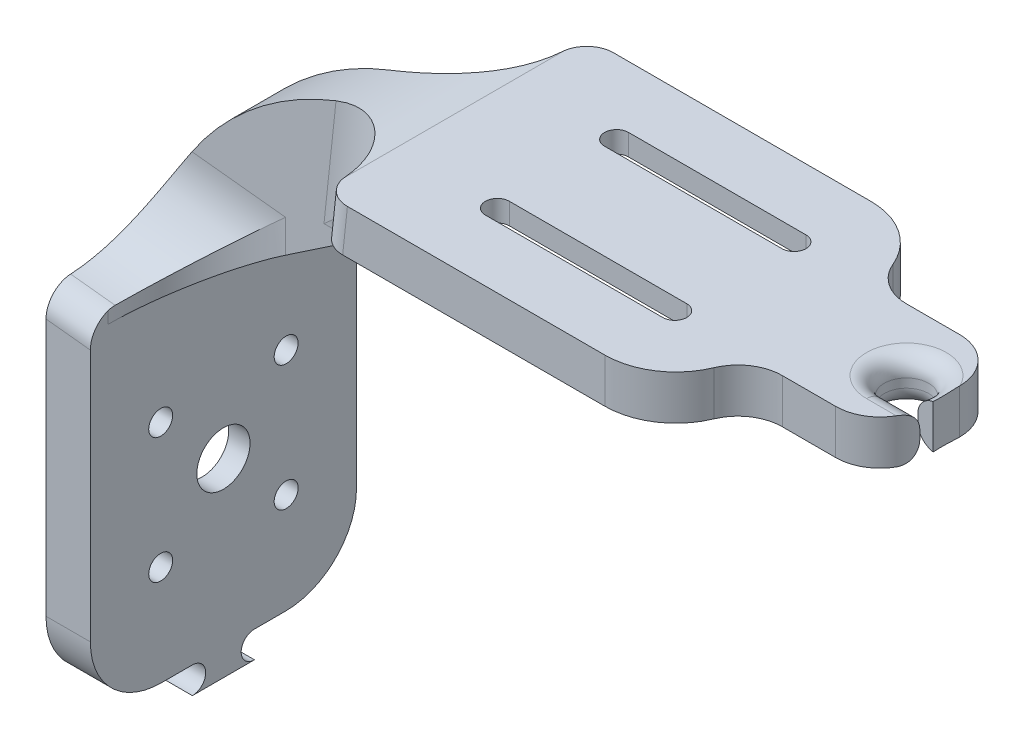
SolidWorks part; units mm, degrees
material "ABS"
ref_plane "Alzado" through (0, 0, 0) normal (0, 0, 1) x (1, 0, 0)
ref_plane "Planta" through (0, 0, 0) normal (0, 1, 0) x (1, 0, 0)
ref_plane "Vista lateral" through (0, 0, 0) normal (1, 0, 0) x (0, 0, -1)
sketch "Croquis1" plane through (0, 0, 0) normal (0, 0, 1) x (1, 0, 0)
  line L0 (0, 0) -> (0, 5)
  line L1 (0, 5) -> (-40, 5)
  line L2 (-40, 5) -> (-71, -20) construction
  line L3 (-71, -20) -> (-71, -60)
  line L4 (-71, -60) -> (-66, -60)
  line L5 (-66, -60) -> (-66, -20.5357)
  line L6 (-66, -20.5357) -> (-40.5357, 0) construction
  line L7 (-40.5357, 0) -> (0, 0)
  line L8 (-53.2679, -10.2679) -> (-37.574, -29.7282) construction
  arc A0 (-40, 5) -> (-71, -20) centre (-37.574, -29.7282) ccw
  arc A1 (-40.5357, 0) -> (-66, -20.5357) centre (-37.574, -29.7282) ccw
  dimension "D1" = 5
  dimension "D2" = 31
  dimension "D4" = 5
  dimension "D5" = 40
  dimension "D6" = 40
  dimension "D7" = 25
  dimension "D8" = 25
extrude "Saliente-Extruir1" add sketch "Croquis1" along normal blind 30
sketch "Croquis2" plane through (0, 5, 0) normal (0, 1, 0) x (1, 0, 0)
  line L0 (0, -30) -> (0, 0) construction
  line L1 (-18.4, -15) -> (-18.4, -12) construction
  line L2 (-18.4, -12) -> (-11.4, -12) construction
  line L4 (-11.4, -18) -> (-25.4, -18) construction
  line L6 (-25.4, -12) -> (-18.4, -12) construction
  line L7 (-18.4, -15) -> (-18.4, -8.28) construction
  line L8 (-18.4, -8.28) -> (-18.4, -6.93) construction
  line L9 (-18.4, -6.93) -> (-8.4, -6.93)
  line L11 (-8.4, -9.63) -> (-28.4, -9.63)
  line L13 (-28.4, -6.93) -> (-18.4, -6.93)
  line L14 (-18.4, -15) -> (-21.0577, -15) construction
  line L22 (0, -15) -> (-18.4, -15) construction
  line L23 (-8.4, -20.37) -> (-28.4, -20.37)
  line L24 (-18.4, -23.07) -> (-8.4, -23.07)
  line L25 (-28.4, -23.07) -> (-18.4, -23.07)
  circle A0 centre (-18.4, -15) radius 18.4 construction
  arc A1 (-25.4, -18) -> (-25.4, -12) centre (-25.4, -15) cw construction
  arc A2 (-11.4, -18) -> (-11.4, -12) centre (-11.4, -15) ccw construction
  arc A3 (-8.4, -9.63) -> (-8.4, -6.93) centre (-8.4, -8.28) ccw
  arc A4 (-28.4, -9.63) -> (-28.4, -6.93) centre (-28.4, -8.28) cw
  arc A9 (-8.4, -20.37) -> (-8.4, -23.07) centre (-8.4, -21.72) cw
  arc A10 (-28.4, -20.37) -> (-28.4, -23.07) centre (-28.4, -21.72) ccw
  dimension "D1" = 36.8
  dimension "D5" = 3
  dimension "D6" = 3
  dimension "D11" = 1.35
  dimension "D12" = 1.35
  dimension "D2" = 18.4
  dimension "D3" = 3
  dimension "D4" = 6
  dimension "D7" = 7
  dimension "D8" = 7
  dimension "D9" = 6.72
  dimension "D10" = 2.7
  dimension "D13" = 10
  dimension "D14" = 10
extrude "Cortar-Extruir1" cut sketch "Croquis2" against normal up to vertex (5 mm away) up to point (0, 0, 30)
sketch "Croquis3" plane through (0, 0, 0) normal (0, -1, 0) x (1, 0, 0)
  line L0 (0, 30) -> (0, 0) construction
  line L5 (-28.4, 9.63) -> (-8.4, 9.63) construction
  line L6 (-33.4, 27.5) -> (-3.4, 27.5)
  line L7 (-33.4, 27.5) -> (-33.4, 2.5)
  line L8 (-33.4, 2.5) -> (-3.4, 2.5)
  line L9 (-3.4, 27.5) -> (-3.4, 2.5)
  line L10 (-33.4, 27.5) -> (-3.4, 2.5) construction
  line L11 (-33.4, 2.5) -> (-3.4, 27.5) construction
  line L12 (0, 15) -> (-18.4, 15) construction
  line L13 (-18.4, 15) -> (-18.4, 9.63) construction
  point P0 (-18.4, 15)
  dimension "D1" = 25
  dimension "D2" = 30
extrude "Cortar-Extruir2" cut sketch "Croquis3" against normal blind 2.6
sketch "Croquis4" plane through (-71, 0, 0) normal (-1, 0, 0) x (0, 0, 1)
  line L0 (30, -60) -> (0, -60) construction
  line L1 (15, -41.6) -> (21.5109, -41.6) construction
  line L3 (22.0711, -34.5289) -> (15, -41.6) construction
  circle A0 centre (15, -41.6) radius 18.4 construction
  circle A1 centre (22.0711, -34.5289) radius 1.35
  circle A2 centre (22.0711, -48.6711) radius 1.35
  circle A3 centre (7.9289, -48.6711) radius 1.35
  circle A4 centre (7.9289, -34.5289) radius 1.35
  circle A5 centre (15, -41.6) radius 3
  point P15 (15, -41.6)
  dimension "D1" = 36.8
  dimension "D5" = 2.7
  dimension "D7" = 6
  dimension "D2" = 18.4
  dimension "D3" = 45
  dimension "D4" = 10
  dimension "D6" = 4
extrude "Cortar-Extruir3" cut sketch "Croquis4" against normal up to vertex (5 mm away) up to point (-66, -60, 30)
sketch "Croquis5" plane through (-71, 0, 0) normal (-1, 0, 0) x (0, 0, 1)
  line L0 (15, -41.6) -> (15, -38.6) construction
  line L1 (2.5, -54.1) -> (27.5, -54.1)
  line L2 (2.5, -54.1) -> (2.5, -29.1)
  line L3 (2.5, -29.1) -> (27.5, -29.1)
  line L4 (27.5, -54.1) -> (27.5, -29.1)
  line L5 (2.5, -54.1) -> (27.5, -29.1) construction
  line L6 (2.5, -29.1) -> (27.5, -54.1) construction
  line L8 (18, -41.6) -> (15, -41.6) construction
  circle A0 centre (15, -41.6) radius 3 construction
  point P0 (15, -41.6)
  dimension "D1" = 25
  dimension "D2" = 25
extrude "Cortar-Extruir4" cut sketch "Croquis5" against normal blind 2.6
sketch "Croquis9" plane through (0, 0, 30) normal (0, 0, 1) x (1, 0, 0)
  line L0 (-40, 5) -> (-40.5357, 0)
  line L1 (-71, -20) -> (-66, -20.5357)
  arc A2 (-40.5357, 0) -> (-66, -20.5357) centre (-37.574, -29.7282) ccw
  arc A3 (-40.5357, 0) -> (-66, -20.5357) centre (-37.574, -29.7282) ccw
  arc A5 (-40, 5) -> (-71, -20) centre (-37.574, -29.7282) ccw
  arc A6 (-40, 5) -> (-71, -20) centre (-37.574, -29.7282) ccw
  dimension "D1" = 0
  dimension "D2" = 0
extrude "Cortar-Extruir5" cut sketch "Croquis9" against normal blind 12
extrude "Cortar-Extruir6" cut sketch "Croquis9<3>" along normal blind 12 from surface starting at face at (-45.1905, -17.7338, 0)
sketch "Croquis9<3>" plane through (0, 0, 30) normal (0, 0, 1) x (1, 0, 0) same geometry as "Croquis9"
sketch "Croquis10" plane through (0, 0, 18) normal (0, 0, 1) x (1, 0, 0)
  line L0 (-66, -60) -> (-66, -22) construction
  line L1 (-66, -60) -> (-66, -20.5357) construction
  line L3 (-40.5357, 0) -> (-33.4, 0)
  line L4 (-33.4, 0) -> (-66, -22)
  line L5 (-66, -22) -> (-66, -20.5357)
  arc A2 (-40.5357, 0) -> (-66, -20.5357) centre (-37.574, -29.7282) ccw
  arc A3 (-40.5357, 0) -> (-66, -20.5357) centre (-37.574, -29.7282) ccw
  dimension "D1" = 38
  dimension "D2" = 0
extrude "Saliente-Extruir3" add sketch "Croquis10" against normal up to surface (6 mm away) up to face at (-56.131, -6.7175, 12)
fillet "Redondeo2" radius 8 4 edges at (-68.5, -60, 0) (-68.5, -60, 30) (0, 2.5, 0) (0, 2.5, 30)
fillet "Redondeo3" radius 2.7 8 edges at (-69.7, -54.1, 2.5) (-69.7, -29.1, 2.5) (-69.7, -29.1, 27.5) (-69.7, -54.1, 27.5) (-33.4, 1.3, 2.5) (-33.4, 1.3, 27.5) (-3.4, 1.3, 27.5) (-3.4, 1.3, 2.5)
sketch "Croquis6" plane through (0, 0, 0) normal (0, -1, 0) x (1, 0, 0)
  line L0 (0, 22) -> (0, 8)
  line L1 (0, 8) -> (15, 8)
  line L2 (15, 8) -> (15, 16)
  line L3 (15, 22) -> (0, 22)
  line L6 (15, 17.5) -> (15, 22)
  line L7 (13.5, 15) -> (13.5, 16) construction
  line L8 (13.5, 16) -> (15, 16) construction
  line L9 (15, 16) -> (13.2913, 16)
  line L10 (13.5, 15) -> (14.5144, 15) construction
  line L11 (11, 17.5) -> (15, 17.5)
  arc A1 (11, 17.5) -> (13.2913, 16) centre (11, 15) ccw
  dimension "D2" = 4
  dimension "D1" = 15
  dimension "D3" = 1
extrude "Saliente-Extruir2" add sketch "Croquis6" against normal up to vertex (5 mm away) up to point (0, 5, 8)
fillet "Redondeo4" radius 5 4 edges at (0, 2.5, 8) (15, 2.5, 8) (15, 2.5, 22) (0, 2.5, 22)
sketch "Croquis7" plane through (-68.4, 0, 0) normal (-1, 0, 0) x (0, 0, 1)
  line L24 (5.2, -54.1) -> (24.8, -54.1)
  line L25 (2.5, -31.8) -> (2.5, -51.4)
  line L26 (24.8, -29.1) -> (5.2, -29.1)
  line L27 (27.5, -51.4) -> (27.5, -31.8)
  line L28 (5.2, -54.1) -> (24.8, -54.1)
  line L29 (2.5, -31.8) -> (2.5, -51.4)
  line L30 (24.8, -29.1) -> (5.2, -29.1)
  line L31 (27.5, -51.4) -> (27.5, -31.8)
  circle A0 centre (22.0711, -34.5289) radius 1.35
  circle A1 centre (15, -41.6) radius 3
  circle A2 centre (22.0711, -48.6711) radius 1.35
  circle A3 centre (7.9289, -34.5289) radius 1.35
  circle A4 centre (7.9289, -48.6711) radius 1.35
  arc A25 (24.8, -54.1) -> (27.5, -51.4) centre (24.8, -51.4) ccw
  arc A26 (2.5, -51.4) -> (5.2, -54.1) centre (5.2, -51.4) ccw
  arc A27 (5.2, -29.1) -> (2.5, -31.8) centre (5.2, -31.8) ccw
  arc A28 (27.5, -31.8) -> (24.8, -29.1) centre (24.8, -31.8) ccw
  arc A29 (24.8, -54.1) -> (27.5, -51.4) centre (24.8, -51.4) ccw
  arc A30 (2.5, -51.4) -> (5.2, -54.1) centre (5.2, -51.4) ccw
  arc A31 (5.2, -29.1) -> (2.5, -31.8) centre (5.2, -31.8) ccw
  arc A32 (27.5, -31.8) -> (24.8, -29.1) centre (24.8, -31.8) ccw
  dimension "D1" = 0
sketch "Croquis8" plane through (0, 2.6, 0) normal (0, -1, 0) x (1, 0, 0)
  line L24 (-3.4, 5.2) -> (-3.4, 24.8)
  line L25 (-30.7, 2.5) -> (-6.1, 2.5)
  line L26 (-33.4, 24.8) -> (-33.4, 5.2)
  line L27 (-6.1, 27.5) -> (-30.7, 27.5)
  line L28 (-3.4, 5.2) -> (-3.4, 24.8)
  line L29 (-30.7, 2.5) -> (-6.1, 2.5)
  line L30 (-33.4, 24.8) -> (-33.4, 5.2)
  line L31 (-6.1, 27.5) -> (-30.7, 27.5)
  line L36 (-28.4, 20.37) -> (-8.4, 20.37)
  line L37 (-8.4, 23.07) -> (-28.4, 23.07)
  line L38 (-28.4, 20.37) -> (-8.4, 20.37)
  line L39 (-8.4, 23.07) -> (-28.4, 23.07)
  line L46 (-28.4, 6.93) -> (-8.4, 6.93)
  line L47 (-8.4, 9.63) -> (-28.4, 9.63)
  line L48 (-28.4, 6.93) -> (-8.4, 6.93)
  line L49 (-8.4, 9.63) -> (-28.4, 9.63)
  arc A20 (-3.4, 24.8) -> (-6.1, 27.5) centre (-6.1, 24.8) ccw
  arc A21 (-6.1, 2.5) -> (-3.4, 5.2) centre (-6.1, 5.2) ccw
  arc A22 (-33.4, 5.2) -> (-30.7, 2.5) centre (-30.7, 5.2) ccw
  arc A23 (-30.7, 27.5) -> (-33.4, 24.8) centre (-30.7, 24.8) ccw
  arc A24 (-3.4, 24.8) -> (-6.1, 27.5) centre (-6.1, 24.8) ccw
  arc A25 (-6.1, 2.5) -> (-3.4, 5.2) centre (-6.1, 5.2) ccw
  arc A26 (-33.4, 5.2) -> (-30.7, 2.5) centre (-30.7, 5.2) ccw
  arc A27 (-30.7, 27.5) -> (-33.4, 24.8) centre (-30.7, 24.8) ccw
  arc A30 (-8.4, 20.37) -> (-8.4, 23.07) centre (-8.4, 21.72) ccw
  arc A31 (-28.4, 23.07) -> (-28.4, 20.37) centre (-28.4, 21.72) ccw
  arc A32 (-8.4, 20.37) -> (-8.4, 23.07) centre (-8.4, 21.72) ccw
  arc A33 (-28.4, 23.07) -> (-28.4, 20.37) centre (-28.4, 21.72) ccw
  arc A38 (-8.4, 6.93) -> (-8.4, 9.63) centre (-8.4, 8.28) ccw
  arc A39 (-28.4, 9.63) -> (-28.4, 6.93) centre (-28.4, 8.28) ccw
  arc A40 (-8.4, 6.93) -> (-8.4, 9.63) centre (-8.4, 8.28) ccw
  arc A41 (-28.4, 9.63) -> (-28.4, 6.93) centre (-28.4, 8.28) ccw
  dimension "D1" = 0
  dimension "D2" = 0
  dimension "D3" = 0
fillet "Redondeo7" radius 10 8 edges at (-68.5, -20.2679, 12) (-40.2679, 2.5, 12) (-40.2679, 2.5, 18) (-68.5, -20.2679, 18) (-66, -21.2679, 12) (-36.9679, 0, 12) (-66, -21.2679, 18) (-36.9679, 0, 18)
fillet "Redondeo8" radius 3 4 edges at (-40.2679, 2.5, 30) (-40.2679, 2.5, 0) (-68.5, -20.2679, 30) (-68.5, -20.2679, 0)
sketch "Croquis11" plane through (-71, 0, 0) normal (-1, 0, 0) x (0, 0, 1)
  line L0 (22, -60) -> (8, -60) construction
  line L1 (11.5, -60) -> (18.5, -60)
  line L3 (11.5, -63) -> (18.5, -63)
  arc A0 (18.5, -60) -> (18.5, -63) centre (18.5, -61.5) ccw
  arc A1 (11.5, -63) -> (11.5, -60) centre (11.5, -61.5) ccw
  point P6 (15, -60)
  point P7 (15, -60)
  point P9 (15, -63)
  dimension "D3" = 1.5
  dimension "D4" = 1.5
  dimension "D1" = 7
  dimension "D2" = 3
extrude "Saliente-Extruir4" add sketch "Croquis11" against normal up to vertex (5 mm away) up to point (-66, -60, 8)
fillet "Redondeo9" radius 2 4 edges at (13, 5, 17.5) (13, 0, 17.5) (9.6307, 5, 12.9083) (9.6307, 0, 12.9083)
fillet "Redondeo10" radius 1 1 edges at (-71, -63, 15)
